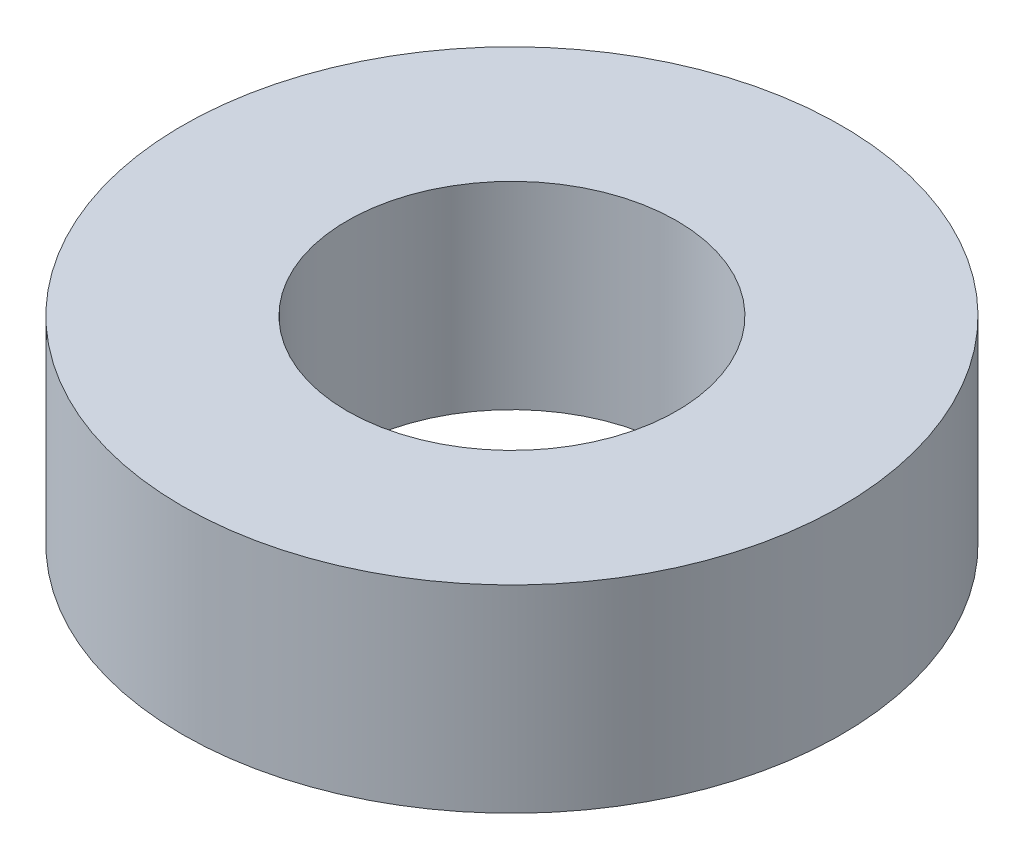
SolidWorks part; units mm, degrees
ref_plane "Front Plane" through (0, 0, 0) normal (0, 0, 1) x (1, 0, 0)
ref_plane "Top Plane" through (0, 0, 0) normal (0, 1, 0) x (1, 0, 0)
ref_plane "Right Plane" through (0, 0, 0) normal (1, 0, 0) x (0, 0, -1)
sketch "Sketch1" plane through (0, 0, 0) normal (0, 1, 0) x (1, 0, 0)
  circle A0 centre (0, 0) radius 25
  dimension "FLANGE_OD" = 50
extrude "Boss-Extrude1" add sketch "Sketch1" along normal blind 15
sketch "Sketch2" plane through (0, 0, 0) normal (0, 1, 0) x (1, 0, 0)
  circle A0 centre (0, 0) radius 12.5
  dimension "BORE_D" = 25
extrude "Cut-Extrude1" cut sketch "Sketch2" along normal through all
sketch "Sketch3" plane through (0, 15, 0) normal (0, 1, 0) x (1, 0, 0)
  circle A0 centre (0, 0) radius 8.6857 construction
  circle A1 centre (-8.6857, 0) radius 2.203
  dimension "BOLT_D" = 4.406
  dimension "BOLT_PCD" = 17.3715
extrude "Cut-Extrude2" cut sketch "Sketch3" against normal blind 13.3732 rebuild error yes
pattern_circular "CirPattern1" count 3 over 360 rebuild error yes
